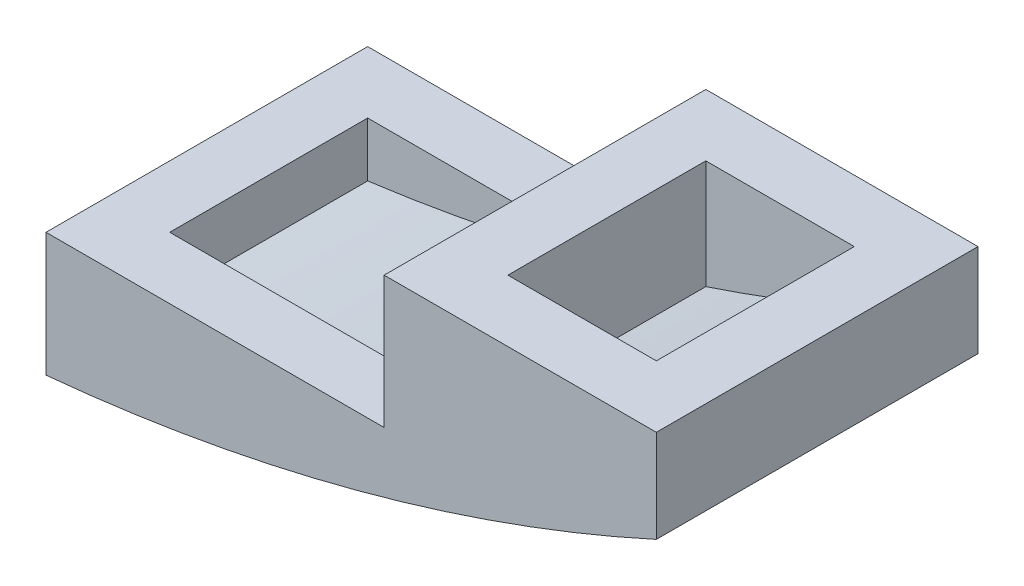
SolidWorks part; units mm, degrees
ref_plane "Front Plane" through (0, 0, 0) normal (0, 0, 1) x (1, 0, 0)
ref_plane "Top Plane" through (0, 0, 0) normal (0, 1, 0) x (1, 0, 0)
ref_plane "Right Plane" through (0, 0, 0) normal (1, 0, 0) x (0, 0, -1)
sketch "Sketch1" plane through (0, 0, 0) normal (0, 0, 1) x (1, 0, 0)
  line L0 (19.1303, -41.9764) -> (19.1303, -39.7264)
  line L1 (19.1303, -39.7264) -> (12.5303, -39.7264)
  line L2 (12.5303, -39.7264) -> (12.5303, -42.9264)
  line L3 (12.5303, -42.9264) -> (4.3303, -42.9264)
  line L4 (4.3303, -42.9264) -> (4.3303, -45.9264)
  arc A0 (4.3303, -45.9264) -> (19.1303, -41.9764) centre (0, 0) ccw
  dimension "D6" = 92.2602
  dimension "D1" = 2.25
  dimension "D2" = 6.6
  dimension "D3" = 3.2
  dimension "D4" = 8.2
  dimension "D5" = 3
extrude "Boss-Extrude1" add sketch "Sketch1" against normal blind 7.8
shell "Shell1" thickness 1.5 removed face at (8.4303, -42.9264, -3.9) removed face at (15.8303, -39.7264, -3.9)
